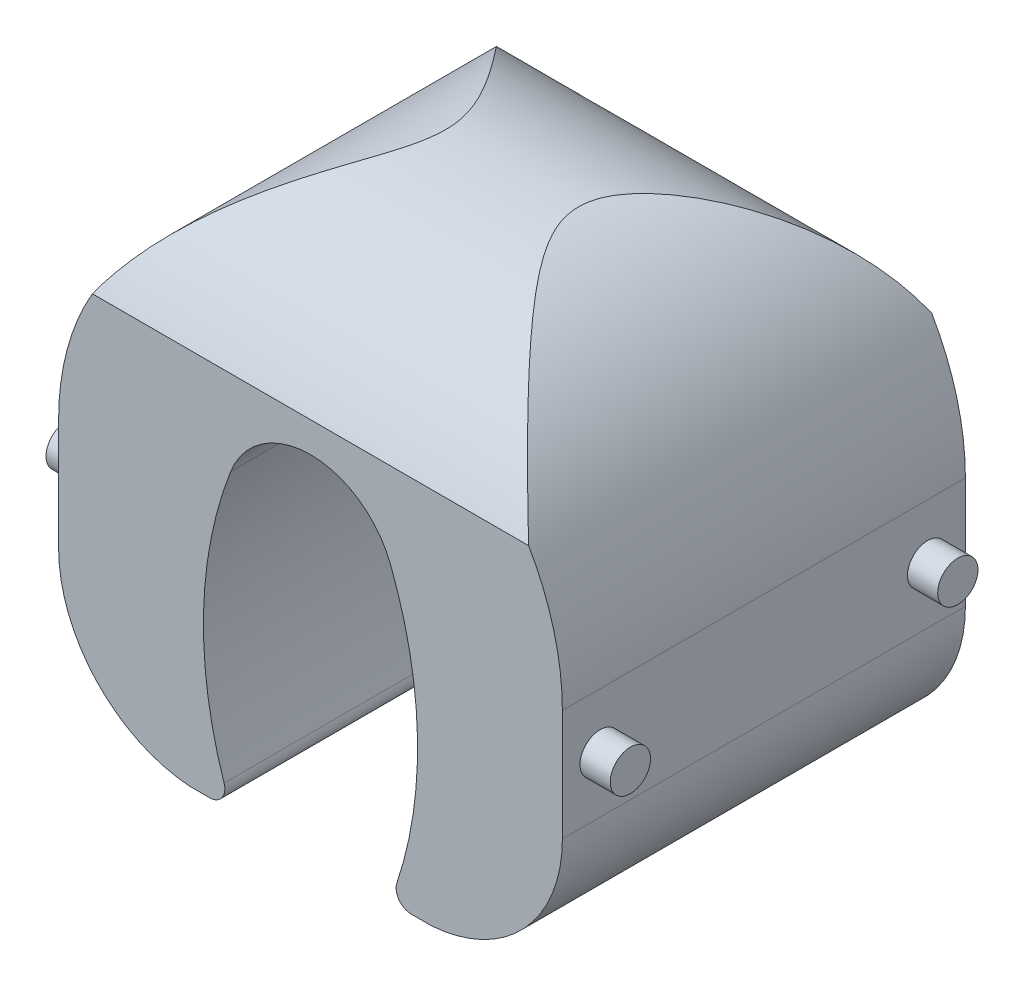
SolidWorks part; units mm, degrees
material "Acrylic (Medium-high impact)"
ref_plane "Front Plane" through (0, 0, 0) normal (0, 0, 1) x (1, 0, 0)
ref_plane "Top Plane" through (0, 0, 0) normal (0, 1, 0) x (1, 0, 0)
ref_plane "Right Plane" through (0, 0, 0) normal (1, 0, 0) x (0, 0, -1)
sketch "Sketch1" plane through (0, 0, 0) normal (0, 0, 1) x (1, 0, 0)
  line L1 (-25, -25) -> (25, -25)
  line L2 (-25, -25) -> (-25, 25)
  line L3 (-25, 25) -> (25, 25)
  line L4 (25, -25) -> (25, 25)
  line L5 (-25, -25) -> (25, 25) construction
  line L6 (-25, 25) -> (25, -25) construction
  point P0 (0, 0)
  dimension "D1" = 50
  dimension "D2" = 50
extrude "Boss-Extrude1" add sketch "Sketch1" along normal blind 60
sketch "Sketch3" plane through (0, 0, 60) normal (0, 0, 1) x (1, 0, 0)
  line L0 (-25, 25) -> (-25, -25) construction
  line L1 (25, -25) -> (25, 25) construction
  line L6 (-25, 0) -> (-25, 25)
  line L7 (-25, 25) -> (25, 25)
  line L8 (25, 25) -> (25, 0)
  arc A0 (-25, 0) -> (25, 0) centre (0, 0) cw
  line M1 (25, -25) -> (25, 25)
  line M2 (25, 25) -> (-25, 25)
  line M3 (-25, 25) -> (-25, -25)
extrude "Cut-Extrude1" cut sketch "Sketch3" against normal up to surface (60 mm away) contours A0 L7 M3 | A0 M2 M1 region at (19.4158, 19.4158, 60) region at (-19.4158, 19.4158, 60) up to face at (0, 0, 0)
sketch "Sketch4" plane through (0, 0, 60) normal (0, 0, 1) x (1, 0, 0)
  line L0 (-25, -25) -> (25, -25) construction
  line L1 (25, -25) -> (25, 0) construction
  line L2 (-25, 0) -> (-25, -25) construction
  line L3 (-25, -25) -> (25, -25)
  line L4 (25, -25) -> (25, -11.0358)
  line L5 (-25, -11.0358) -> (-25, -25)
  line L6 (0, 22.8137) -> (0, -21.5771) construction
  arc A0 (-25, -11.0358) -> (-10, -25) centre (-11, -11.0358) ccw
  arc A1 (25, -11.0358) -> (10, -25) centre (11, -11.0358) cw
  arc A2 (-10, -25) -> (-8.5769, -23.0258) centre (-10, -23.5) ccw
  arc A3 (10, -25) -> (8.5769, -23.0258) centre (10, -23.5) cw
  arc A4 (-8.5769, -23.0258) -> (-7.9258, 4.0712) centre (29.372, -10.3814) cw
  arc A5 (8.5769, -23.0258) -> (7.9258, 4.0712) centre (-29.372, -10.3814) ccw
  arc A6 (-7.9258, 4.0712) -> (7.9258, 4.0712) centre (0, 1) cw
  arc A7 (25, 0) -> (-25, 0) centre (0, 0) ccw construction
  line M2 (25, -25) -> (25, 0)
  line M4 (-25, 0) -> (-25, -25)
  line M5 (-25, -25) -> (25, -25)
  dimension "D1" = 14
  dimension "D2" = 20
  dimension "D3" = 40
  dimension "D4" = 8.5
  dimension "D5" = 1
  dimension "D6" = 1.5
extrude "Cut-Extrude2" cut sketch "Sketch4" against normal up to surface (60 mm away) contours A6 A4 A2 A3 A5 M5 | A0 M4 M5 | A1 M2 M5 region at (0, -8.8337, 60) region at (-21.9135, -21.873, 60) region at (21.9135, -21.873, 60) up to face at (0, -6.25, 0)
sketch "Sketch5" plane through (0, 0, 60) normal (0, 0, 1) x (1, 0, 0)
  line L0 (-7.9258, 4.0712) -> (-12.8794, 4.0712)
  line L1 (-12.8794, 4.0712) -> (-12.8794, -5.9288)
  line L2 (-12.8794, -5.9288) -> (-10.3794, -5.9288)
  line L3 (7.9258, 4.0712) -> (12.8794, 4.0712)
  line L4 (12.8794, 4.0712) -> (12.8794, -5.9288)
  line L5 (12.8794, -5.9288) -> (10.3794, -5.9288)
  arc A0 (8.5769, -23.0258) -> (7.9258, 4.0712) centre (-29.372, -10.3814) ccw construction
  arc A1 (-7.9258, 4.0712) -> (-8.5769, -23.0258) centre (29.372, -10.3814) ccw construction
  arc A2 (10.3794, -5.9288) -> (7.9258, 4.0712) centre (-29.372, -10.3814) ccw
  arc A3 (-7.9258, 4.0712) -> (-10.3794, -5.9288) centre (29.372, -10.3814) ccw
  dimension "D1" = 10
  dimension "D2" = 10
  dimension "D3" = 2.5
  dimension "D4" = 2.5
extrude "Cut-Extrude3" cut sketch "Sketch5" against normal blind 10 flip side to cut
sketch "Sketch6" plane through (0, 0, 0) normal (0, 0, -1) x (-1, 0, 0)
  line L1 (12.8794, 4.0712) -> (12.8794, -5.9288) construction
  line L4 (-12.8794, 4.0712) -> (-12.8794, -5.9288) construction
  line L7 (12.8794, 3.0712) -> (12.8794, -4.9288)
  line L10 (-12.8794, 3.0712) -> (-12.8794, -4.9288)
  line L14 (-15.8794, 5.0712) -> (-15.8794, -6.9324)
  line L16 (12.8794, 3.0712) -> (12.8794, 6.0712)
  line L17 (0, 26.9146) -> (0, -26.5291) construction
  line L18 (15.8794, 5.0712) -> (15.8794, -6.9324)
  line L19 (12.8794, 6.0712) -> (14.8794, 6.0712)
  line L20 (-12.8794, 3.0712) -> (-12.8794, 6.0712)
  line L21 (-12.8794, 6.0712) -> (-14.8794, 6.0712)
  line L22 (-12.8794, -4.9288) -> (-12.8794, -7.9324)
  line L23 (-12.8794, -7.9324) -> (-14.8794, -7.9324)
  line L24 (12.8794, -4.9288) -> (12.8794, -7.9324)
  line L25 (12.8794, -7.9324) -> (14.8794, -7.9324)
  arc A1 (-7.9258, 4.0712) -> (-10.3794, -5.9288) centre (29.372, -10.3814) ccw construction
  arc A4 (-7.9258, 4.0712) -> (-8.5769, -23.0258) centre (29.372, -10.3814) ccw construction
  arc A5 (-10.3794, -5.9288) -> (-8.5769, -23.0258) centre (29.372, -10.3814) ccw
  arc A6 (-10.553, -7.9324) -> (-10.3794, -5.9288) centre (29.372, -10.3814) cw
  arc A11 (-15.8794, -6.9324) -> (-14.8794, -7.9324) centre (-14.8794, -6.9324) ccw
  arc A12 (-14.8794, 6.0712) -> (-15.8794, 5.0712) centre (-14.8794, 5.0712) ccw
  arc A15 (15.8794, -6.9324) -> (14.8794, -7.9324) centre (14.8794, -6.9324) cw
  arc A17 (14.8794, 6.0712) -> (15.8794, 5.0712) centre (14.8794, 5.0712) cw
  point P34 (-15.8794, -7.9324)
  point P37 (-15.8794, 6.0712)
  arc M9 (8.5769, -23.0258) -> (10, -25) centre (10, -23.5) ccw
  arc M10 (12, -25) -> (25, -11.0358) centre (11, -11.0358) ccw
  line M11 (25, -11.0358) -> (25, 0)
  arc M12 (25, 0) -> (-25, 0) centre (0, 0) ccw
  line M13 (-25, 0) -> (-25, -11.0358)
  arc M14 (-25, -11.0358) -> (-12, -25) centre (-11, -11.0358) ccw
  arc M15 (-10, -25) -> (-8.5769, -23.0258) centre (-10, -23.5) ccw
  arc M16 (-8.5769, -23.0258) -> (-7.9258, 4.0712) centre (29.372, -10.3814) cw
  arc M17 (-7.9258, 4.0712) -> (7.9258, 4.0712) centre (0, 1) cw
  arc M18 (7.9258, 4.0712) -> (8.5769, -23.0258) centre (-29.372, -10.3814) cw
  line M20 (-12, -25) -> (-10, -25)
  line M21 (10, -25) -> (12, -25)
  dimension "D1" = 3
extrude "Cut-Extrude4" cut sketch "Sketch6" against normal blind 10 contours L17 L14 L10 M12 M13 M14 M20 M15 M16 M17 | L17 L7 L18 M12 M17 M18 M9 M21 M10 M11 | L10 M16 | L7 M18 region at (-17.2824, 17.2824, 0) region at (0.559, 17.25, 0)
fillet "Fillet1" radius 1 4 edges at (12.8794, 4.0712, 55) (12.8794, -5.9288, 55) (-12.8794, -5.9288, 55) (-12.8794, 4.0712, 55)
sketch "Sketch7" plane through (-12.8794, 0, 0) normal (-1, 0, 0) x (0, 0, 1)
  line L0 (55, 3.0712) -> (55, -4.9288) construction
  line L1 (60, 3.0712) -> (50, 3.0712) construction
  line L2 (50, -4.9288) -> (60, -4.9288) construction
  line L3 (60, -0.9288) -> (50, -0.9288) construction
  line L4 (60, -5.9288) -> (60, 4.0712) construction
  line L5 (50, 3.0712) -> (50, -4.9288) construction
  circle A0 centre (55, -0.9288) radius 2
  dimension "D1" = 4
extrude "Boss-Extrude2" add sketch "Sketch7" along normal blind 2
sketch "Sketch8" plane through (12.8794, 0, 0) normal (1, 0, 0) x (0, 0, -1)
  line L0 (-55, 3.0712) -> (-55, -4.9288) construction
  line L1 (-50, 3.0712) -> (-60, 3.0712) construction
  line L2 (-60, -4.9288) -> (-50, -4.9288) construction
  line L3 (-60, -0.9288) -> (-50, -0.9288) construction
  line L4 (-60, 4.0712) -> (-60, -5.9288) construction
  line L5 (-50, -4.9288) -> (-50, 3.0712) construction
  circle A0 centre (-55, -0.9288) radius 2
  dimension "D1" = 4
extrude "Boss-Extrude3" add sketch "Sketch8" along normal blind 2
sketch "Sketch9" plane through (12.8794, 0, 0) normal (-1, 0, 0) x (0, 0, 1)
  line L0 (5, 5.0712) -> (5, -6.9324) construction
  line L1 (10, 5.0712) -> (0, 5.0712) construction
  line L2 (10, -6.9324) -> (0, -6.9324) construction
  line L3 (0, -0.9306) -> (10, -0.9306) construction
  line L4 (0, 5.0712) -> (0, -6.9324) construction
  line L5 (10, 5.0712) -> (10, -6.9324) construction
  circle A0 centre (5, -0.9306) radius 2.25
  dimension "D1" = 4.5
extrude "Cut-Extrude5" cut sketch "Sketch9" against normal blind 2
sketch "Sketch10" plane through (-12.8794, 0, 0) normal (1, 0, 0) x (0, 0, -1)
  line L0 (-5, 5.0712) -> (-5, -6.9324) construction
  line L1 (-10, 5.0712) -> (0, 5.0712) construction
  line L2 (-10, -6.9324) -> (0, -6.9324) construction
  line L3 (-10, -0.9306) -> (0, -0.9306) construction
  line L4 (-10, 5.0712) -> (-10, -6.9324) construction
  line L5 (0, 5.0712) -> (0, -6.9324) construction
  circle A0 centre (-5, -0.9306) radius 2.25
  dimension "D1" = 4.5
extrude "Cut-Extrude6" cut sketch "Sketch10" against normal blind 2
fillet "Fillet2" radius 1 4 edges at (-12.8794, -7.9324, 5) (-12.8794, 6.0712, 5) (12.8794, -7.9324, 5) (12.8794, 6.0712, 5)
sketch "Sketch11" plane through (0, 0, 0) normal (1, 0, 0) x (0, 0, -1)
  line L0 (-10, 0) -> (-10, 25) construction
  line L1 (-10, 5.0712) -> (0, 5.0712) construction
  line L2 (0, 5.0712) -> (0, -6.9324) construction
  line L3 (-10, 0) -> (-10, 25)
  line L4 (-10, 5.0712) -> (0, 5.0712)
  line L5 (0, 5.0712) -> (0, -6.9324)
  line L6 (-50, 25) -> (-50, 0) construction
  line L7 (-50, 25) -> (-50, 0)
  line L8 (-30, 12.5) -> (-30, 36.2918) construction
  line L9 (-50, 25) -> (-10, 25)
  line L10 (-10, 25) -> (-10, 12.5)
  line L11 (-50, 25) -> (-50, 12.5)
  arc A0 (-10, 12.5) -> (-30, 32.5) centre (-30, 12.5) ccw
  spline S0 degree 3 poles (-50, 12.5) (-41.6701, 27.9801) (-18.3299, 27.9801) (-10, 12.5) knots 0 0 0 0 1 1 1 1
  dimension "D2" = 48.6
  dimension "D1" = 4.5
extrude "Cut-Extrude7" cut sketch "Sketch11" along normal up to surface and the other way up to surface contours S0 L8 L9 L7 | L8 S0 A0 L9 | A0 L3 L9 region at (0, 21.9477, 11.2872) region at (0, 21.5983, 16.9845) region at (0, 21.671, 44.2013) up to face at (0, 12.5, 30) other way up to face at (0, 12.5, 30)
sketch "Sketch12" plane through (14.8794, 0, 0) normal (1, 0, 0) x (0, 0, -1)
  line L1 (-60, -5.9288) -> (-50, -5.9288)
  line L2 (-60, -5.9288) -> (-60, 4.0712)
  line L3 (-60, 4.0712) -> (-50, 4.0712)
  line L4 (-50, -5.9288) -> (-50, 4.0712)
extrude "Cut-Extrude8" cut sketch "Sketch12" against normal up to surface (29.7589 mm away) up to face at (-14.8794, -2.9288, 55)
sketch "Sketch13" plane through (15.8794, 0, 0) normal (1, 0, 0) x (0, 0, -1)
  line L1 (-10, -7.9324) -> (0, -7.9324)
  line L2 (-10, -7.9324) -> (-10, 6.0712)
  line L3 (-10, 6.0712) -> (0, 6.0712)
  line L4 (0, -7.9324) -> (0, 6.0712)
extrude "Cut-Extrude9" cut sketch "Sketch13" against normal up to surface (31.7589 mm away) up to face at (-15.8794, -0.9306, 5)
sketch "Sketch14" plane through (25, 0, 0) normal (1, 0, 0) x (0, 0, -1)
  line L0 (-30, 0) -> (-30, -11.0358) construction
  line L1 (-50, -5.5179) -> (-10, -5.5179) construction
  line L2 (-17.5, 0) -> (-17.5, -11.0358) construction
  line L3 (-13.75, 0) -> (-13.75, -11.0358) construction
  line L4 (-10, -11.0358) -> (-10, 0)
  line L5 (-10, 0) -> (-50, 0)
  line L6 (-50, 0) -> (-50, -11.0358)
  line L7 (-50, -11.0358) -> (-10, -11.0358)
  line L8 (-10, -11.0358) -> (-10, 0)
  line L9 (-10, 0) -> (-50, 0)
  line L10 (-50, 0) -> (-50, -11.0358)
  line L11 (-50, -11.0358) -> (-10, -11.0358)
  line L12 (-46.25, 0) -> (-46.25, -11.0358) construction
  circle A0 centre (-13.75, -5.5179) radius 2
  circle A1 centre (-46.25, -5.5179) radius 2
  dimension "D4" = 4
  dimension "D6" = 4
  dimension "D2" = 7.5
  dimension "D3" = 3.75
  dimension "D5" = 3.75
  dimension "D1" = 0
extrude "Boss-Extrude4" add sketch "Sketch14" along normal blind 3 contours A0 | A1
sketch "Sketch15" plane through (-25, 0, 0) normal (-1, 0, 0) x (0, 0, 1)
  line L0 (10, -5.5179) -> (50, -5.5179) construction
  line L1 (30, 0) -> (30, -11.0358) construction
  line L2 (13.75, 0) -> (13.75, -11.0358) construction
  line L3 (46.25, 0) -> (46.25, -11.0358) construction
  line L4 (10, 0) -> (10, -11.0358)
  line L5 (10, -11.0358) -> (50, -11.0358)
  line L6 (50, -11.0358) -> (50, 0)
  line L7 (50, 0) -> (10, 0)
  line L8 (10, 0) -> (10, -11.0358)
  line L9 (10, -11.0358) -> (50, -11.0358)
  line L10 (50, -11.0358) -> (50, 0)
  line L11 (50, 0) -> (10, 0)
  circle A0 centre (13.75, -5.5179) radius 2
  circle A1 centre (46.25, -5.5179) radius 2
  dimension "D3" = 4
  dimension "D5" = 4
  dimension "D2" = 3.75
  dimension "D4" = 3.75
  dimension "D1" = 0
extrude "Boss-Extrude5" add sketch "Sketch15" along normal blind 3 contours A0 | A1
